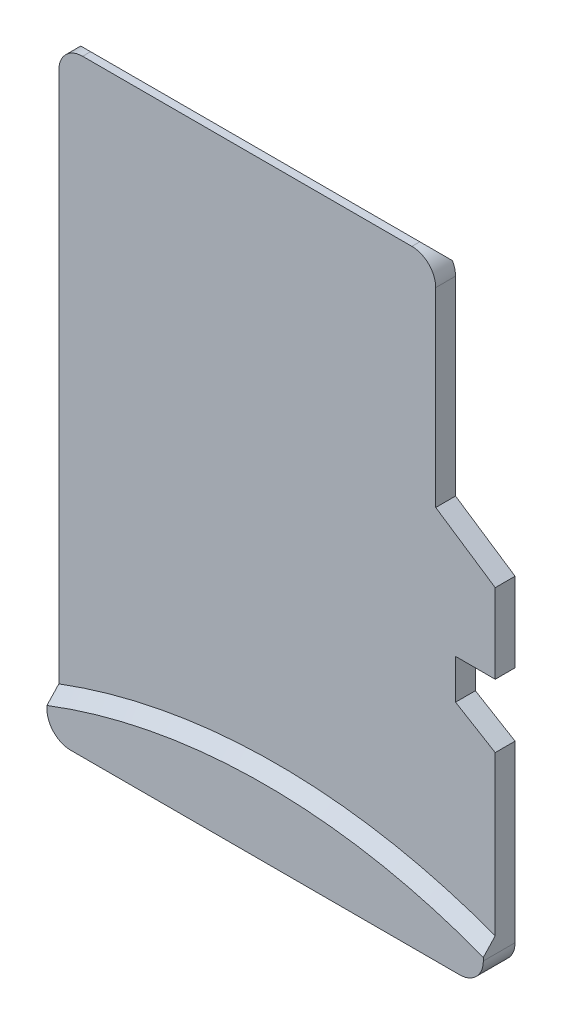
SolidWorks part; units mm, degrees
other "Câmera1"
other "Câmera2"
ref_plane "Plano frontal" through (0, 0, 0) normal (0, 0, 1) x (1, 0, 0)
ref_plane "Plano superior" through (0, 0, 0) normal (0, 1, 0) x (1, 0, 0)
ref_plane "Plano direito" through (0, 0, 0) normal (1, 0, 0) x (0, 0, -1)
sketch "Esboço1" plane through (0, 0, 0) normal (0, 0, 1) x (1, 0, 0)
  line L0 (0, 9.4451) -> (0, -9.4451) construction
  line L1 (-16.605, 0) -> (16.605, 0) construction
  line L2 (-4.376, -7.111) -> (-4.376, 6.689)
  line L3 (-3.776, 7.289) -> (4.524, 7.289)
  line L4 (5.124, 6.689) -> (5.124, 1.889)
  line L5 (5.124, 1.889) -> (6.624, 0.889)
  line L6 (6.624, 0.889) -> (6.624, -1.111)
  line L7 (6.624, -1.111) -> (5.624, -1.111)
  line L8 (5.624, -1.111) -> (5.624, -2.111)
  line L9 (5.624, -2.111) -> (6.624, -2.711)
  line L10 (6.624, -2.711) -> (6.624, -7.111)
  line L11 (6.024, -7.711) -> (-3.776, -7.711)
  arc A0 (4.524, 7.289) -> (5.124, 6.689) centre (4.524, 6.689) cw
  arc A1 (-4.376, 6.689) -> (-3.776, 7.289) centre (-3.776, 6.689) cw
  arc A2 (6.624, -7.111) -> (6.024, -7.711) centre (6.024, -7.111) cw
  arc A3 (-3.776, -7.711) -> (-4.376, -7.111) centre (-3.776, -7.111) cw
  point P17 (5.124, 7.289)
  point P20 (-4.376, 7.289)
  point P23 (6.624, -7.711)
  point P26 (-4.376, -7.711)
  dimension "D10" = 0.6
  dimension "D1" = 15
  dimension "D2" = 9.5
  dimension "D3" = 11
  dimension "D4" = 5
  dimension "D5" = 0.6
  dimension "D6" = 1
  dimension "D7" = 2
  dimension "D8" = 1
  dimension "D9" = 1
extrude "Ressalto-extrusão1" add sketch "Esboço1" along normal blind 0.5
sketch "Esboço2" plane through (0, 0, 0.5) normal (0, 0, 1) x (1, 0, 0)
  line L0 (-3.776, -7.711) -> (6.024, -7.711)
  line L1 (-4.376, -7.111) -> (-4.376, -6.711)
  line L2 (-4.376, 6.689) -> (-4.376, -7.111) construction
  line L3 (0, 9.0051) -> (0, -15.1009) construction
  line L4 (6.624, -7.111) -> (6.624, -6.711)
  line L5 (6.624, -7.111) -> (6.624, -2.711) construction
  line L6 (-5.7133, -5.711) -> (6.9927, -5.711) construction
  arc A0 (6.024, -7.711) -> (6.624, -7.111) centre (6.024, -7.111) ccw
  arc A1 (6.024, -7.711) -> (6.624, -7.111) centre (6.024, -7.111) ccw construction
  arc A2 (-3.776, -7.711) -> (-4.376, -7.111) centre (-3.776, -7.111) cw
  arc A3 (6.624, -6.711) -> (-4.376, -6.711) centre (1.124, -21.336) ccw
  dimension "D1" = 1
  dimension "D2" = 2
  dimension "D3" = 1
extrude "Ressalto-extrusão2" add sketch "Esboço2" along normal blind 0.3
sketch "Esboço5" plane through (5.124, 0, 0) normal (1, 0, 0) x (0, 0, -1)
  line L0 (0, 7.289) -> (-0.3, 7.289)
  line L1 (-0.5, 7.289) -> (0, 7.289) construction
  line L2 (0, 7.289) -> (0, 6.989)
  line L3 (0, 6.689) -> (0, 7.289) construction
  line L4 (-0.3, 7.289) -> (0, 6.989)
  dimension "D1" = 0.3
  dimension "D2" = 0.3
extrude "Corte-extrusão2" cut sketch "Esboço5" against normal blind 10
sketch "Esboço6" plane through (0, 0, 0) normal (0, 0, -1) x (-1, 0, 0)
  line L0 (-0.374, 9.2565) -> (-0.374, -9.6226) construction
  line L1 (-5.0436, 6.989) -> (4.2957, 6.989) construction
  line L2 (-4.674, 6.489) -> (-3.774, 6.489)
  line L3 (-4.674, 6.489) -> (-4.674, 3.489)
  line L4 (-4.674, 3.489) -> (-3.774, 3.489)
  line L5 (-3.774, 6.489) -> (-3.774, 3.489)
  line L6 (-5.124, 1.889) -> (-5.124, 6.689) construction
  line L7 (-3.574, 6.489) -> (-3.574, 3.489)
  line L8 (-3.574, 6.489) -> (-2.674, 6.489)
  line L9 (-2.674, 6.489) -> (-2.674, 3.489)
  line L10 (-3.574, 3.489) -> (-2.674, 3.489)
  line L11 (-2.474, 6.489) -> (-2.474, 3.489)
  line L12 (-2.474, 6.489) -> (-1.574, 6.489)
  line L13 (-1.574, 6.489) -> (-1.574, 3.489)
  line L14 (-2.474, 3.489) -> (-1.574, 3.489)
  line L15 (-1.374, 6.489) -> (-1.374, 3.489)
  line L17 (-0.474, 6.489) -> (-0.474, 3.489)
  line L18 (-1.374, 3.489) -> (-0.474, 3.489)
  line L19 (-0.274, 6.489) -> (-0.274, 3.489)
  line L20 (-0.274, 6.489) -> (0.626, 6.489)
  line L21 (0.626, 6.489) -> (0.626, 3.489)
  line L22 (-0.274, 3.489) -> (0.626, 3.489)
  line L23 (0.826, 6.489) -> (0.826, 3.489)
  line L25 (1.726, 6.489) -> (1.726, 3.489)
  line L26 (0.826, 3.489) -> (1.726, 3.489)
  line L27 (1.926, 6.489) -> (1.926, 3.489)
  line L28 (1.926, 6.489) -> (2.826, 6.489)
  line L29 (2.826, 6.489) -> (2.826, 3.489)
  line L30 (1.926, 3.489) -> (2.826, 3.489)
  line L31 (3.026, 6.489) -> (3.026, 3.489)
  line L32 (3.026, 6.489) -> (3.926, 6.489)
  line L33 (3.926, 6.489) -> (3.926, 3.489)
  line L34 (3.026, 3.489) -> (3.926, 3.489)
  line L37 (-1.374, 6.489) -> (-1.374, 6.889)
  line L38 (-1.374, 6.889) -> (-0.474, 6.889)
  line L39 (-0.474, 6.889) -> (-0.474, 6.489)
  line L40 (0.826, 6.489) -> (0.826, 6.889)
  line L41 (0.826, 6.889) -> (1.726, 6.889)
  line L42 (1.726, 6.889) -> (1.726, 6.489)
  line L44 (-1.374, 6.489) -> (-0.474, 6.489) [skipped]
  line L45 (0.826, 6.489) -> (1.726, 6.489) [skipped]
  dimension "D1" = 3
  dimension "D2" = 0.9
  dimension "D3" = 0.5
  dimension "D4" = 0.45
  dimension "D6" = 0.4
  dimension "D5" = 8
extrude "Ressalto-extrusão3" add sketch "Esboço6" along normal blind 0.02
chamfer "Chanfro4" distance 0.3 angle 45 1 edges at (1.124, -5.711, 0.8)
